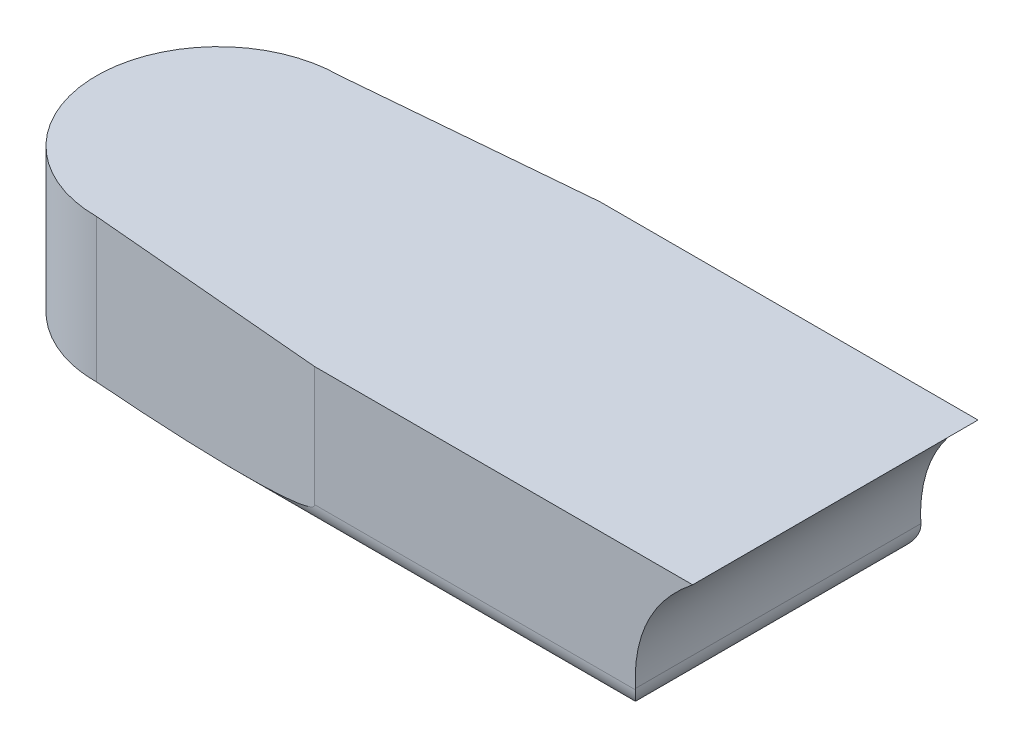
SolidWorks part; units mm, degrees
ref_plane "前视基准面" through (0, 0, 0) normal (0, 0, 1) x (1, 0, 0)
ref_plane "上视基准面" through (0, 0, 0) normal (0, 1, 0) x (1, 0, 0)
ref_plane "右视基准面" through (0, 0, 0) normal (1, 0, 0) x (0, 0, -1)
sketch "草图3" plane through (0, 0, 0) normal (0, 1, 0) x (1, 0, 0)
  line L0 (163.7303, -29.8251) -> (80.5797, -29.8251)
  line L1 (80.5797, -29.8251) -> (30.5797, -25.4506)
  line L2 (30.5797, 25.4506) -> (80.5797, 29.8251)
  line L3 (80.5797, 29.8251) -> (163.7303, 29.8251)
  line L4 (163.7303, 29.8251) -> (163.7303, -29.8251)
  line L5 (30.5797, -25.4506) -> (30.5797, 25.4506) construction
  line L7 (80.5797, 29.8251) -> (0, 25.6021) construction
  line L8 (0, -25.6021) -> (80.5797, -29.8251) construction
  arc A0 (30.5797, -25.4506) -> (30.5797, 25.4506) centre (30.5797, 0) cw
  dimension "D1" = 50
  dimension "D2" = 50
  dimension "D3" = 2
  dimension "D4" = 2
extrude "凸台-拉伸1" add sketch "草图3" against normal blind 30 contours A0 L2 L3 L4 L0 L1
sketch "草图4" plane through (0, 0, 0) normal (0, 0, 1) x (1, 0, 0)
  line L0 (163.7303, 0) -> (159.5807, 0)
  line L1 (163.7303, 0) -> (80.5797, 0) construction
  line L2 (163.7303, -30) -> (80.5797, -30) construction
  line L3 (148.3027, -30) -> (203.2217, -30)
  line L4 (203.2217, -30) -> (203.2217, 0)
  line L5 (203.2217, 0) -> (163.7303, 0)
  spline S0 degree 2 poles (159.5807, 0) (144.6445, -11.8398) (148.3027, -30) knots 0 0 0 1 1 1
extrude "切除-拉伸1" cut sketch "草图4" against normal through all both and the other way through all
fillet "圆角1" radius 5 3 edges at (148.3027, -30, 0) (114.4412, -30, -29.8251) (114.4412, -30, 29.8251)
